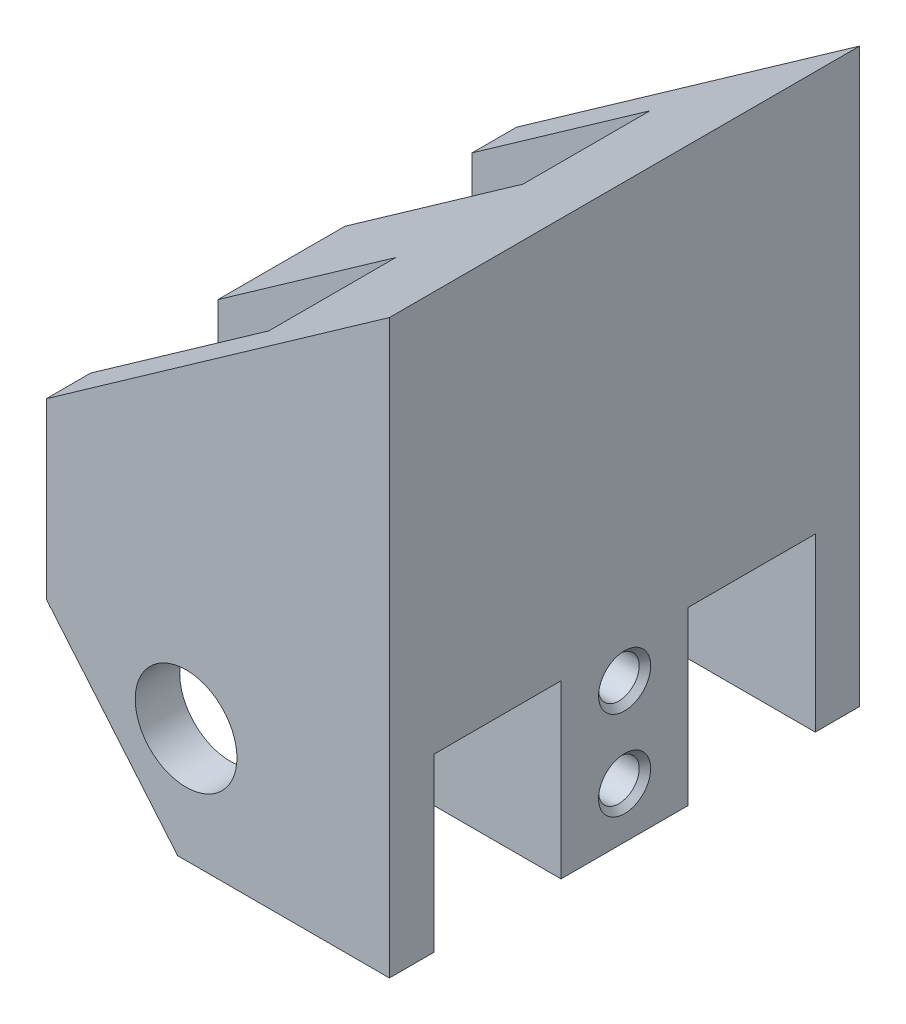
SolidWorks part; units mm, degrees
ref_plane "Front Plane" through (0, 0, 0) normal (0, 0, 1) x (1, 0, 0)
ref_plane "Top Plane" through (0, 0, 0) normal (0, 1, 0) x (1, 0, 0)
ref_plane "Right Plane" through (0, 0, 0) normal (1, 0, 0) x (0, 0, -1)
sketch "Sketch1" plane through (0, 0, 0) normal (0, 0, 1) x (1, 0, 0)
  line L0 (-7.2764, -10.5186) -> (2.2236, -16.0034)
  line L1 (2.2236, -16.0034) -> (6.2236, -16.0034)
  line L2 (-7.2764, -10.5186) -> (-7.2764, -0.5186)
  line L4 (6.2236, -16.0034) -> (6.2236, 8.9966)
  line L5 (-7.2764, -10.5186) -> (6.2236, 8.9966) construction
  line L6 (-1.4071, 3.6183) -> (6.2236, -16.0034) construction
  line L7 (-7.2764, -0.5186) -> (6.2236, 8.9966)
  point P0 (0, 0)
  dimension "D1" = 13.5
  dimension "D2" = 25
  dimension "D3" = 4
  dimension "D4" = 30
  dimension "D5" = 10
extrude "Boss-Extrude1" add sketch "Sketch1" along normal blind 18.5
sketch "Sketch2" plane through (0, 0, 0) normal (0, 0, -1) x (-1, 0, 0)
  line L0 (7.2764, -0.5186) -> (7.2764, -10.5186) construction
  line L1 (-6.2236, -16.0034) -> (-6.2236, 8.9966) construction
  line L3 (-2.2236, -16.0034) -> (-6.2236, -16.0034) construction
  circle A0 centre (1.7764, -9.0034) radius 2
  circle A1 centre (-2.2236, -5.0034) radius 1.5
  dimension "D1" = 4
  dimension "D2" = 3
  dimension "D3" = 5.5
  dimension "D4" = 4
  dimension "D5" = 7
  dimension "D6" = 11
extrude "Cut-Extrude1" cut sketch "Sketch2" against normal through all contours A0 region at (-1.7764, -9.0034, 0)
extrude "Cut-Extrude2" cut sketch "Sketch2<3>" against normal blind 11 contours A1 region at (2.2236, -5.0034, 0)
sketch "Sketch2<3>" plane through (0, 0, 0) normal (0, 0, -1) x (-1, 0, 0) same geometry as "Sketch2"
sketch "Sketch5" plane through (0, 0, 0) normal (0, 0, -1) x (-1, 0, 0)
  line L0 (-6.2236, -13.5034) -> (2.1066, -13.5034)
  line L1 (-6.2236, -16.0034) -> (-6.2236, 8.9966) construction
  line L2 (7.2764, -10.5186) -> (-2.2236, -16.0034) construction
  line L3 (2.1066, -13.5034) -> (-2.2236, -16.0034)
  line L4 (-2.2236, -16.0034) -> (-6.2236, -16.0034)
  line L5 (-6.2236, -16.0034) -> (-6.2236, -13.5034)
  dimension "D1" = 2.5
extrude "Cut-Extrude3" cut sketch "Sketch5" against normal through all
sketch "Sketch6" plane through (0, 0, 0) normal (0, 0, -1) x (-1, 0, 0)
  line L0 (2.1066, -13.5034) -> (7.2764, -7.3422)
  line L1 (7.2764, -0.5186) -> (7.2764, -10.5186) construction
  line L2 (7.2764, -7.3422) -> (7.2764, -10.5186)
  line L3 (7.2764, -10.5186) -> (2.1066, -13.5034)
  dimension "D1" = 20
extrude "Cut-Extrude4" cut sketch "Sketch6" against normal through all
sketch "Sketch7" plane through (6.2236, 0, 0) normal (1, 0, 0) x (0, 0, -1)
  line L0 (-9.25, 8.9966) -> (-9.25, -14.2492) construction
  line L1 (-18.5, 8.9966) -> (0, 8.9966) construction
  line L2 (-18.5, -13.5034) -> (0, -13.5034) construction
  line L3 (-16.75, -13.5034) -> (-11.75, -13.5034)
  line L4 (-16.75, -13.5034) -> (-16.75, -6.7534)
  line L5 (-16.75, -6.7534) -> (-11.75, -6.7534)
  line L6 (-11.75, -13.5034) -> (-11.75, -6.7534)
  line L7 (-1.75, -6.7534) -> (-6.75, -6.7534)
  line L8 (-6.75, -13.5034) -> (-6.75, -6.7534)
  line L9 (-1.75, -13.5034) -> (-6.75, -13.5034)
  line L10 (-1.75, -13.5034) -> (-1.75, -6.7534)
  line M7 (-18.5, -13.5034) -> (0, -13.5034)
  dimension "D1" = 6.75
  dimension "D2" = 5
  dimension "D3" = 2.5
extrude "Cut-Extrude5" cut sketch "Sketch7" against normal through all contours L6 L5 L4 M7 | L10 L7 L8 M7 region at (6.2236, -10.1284, 14.25) region at (6.2236, -10.1284, 4.25)
hole_wizard "M2x0.4 Tapped Hole1" positions "Sketch9" profile "Sketch10" tap size "M2x0.4" standard "ANSI Metric"
sketch "Sketch9" plane through (6.2236, 0, 0) normal (1, 0, 0) x (0, 0, -1)
  line L0 (-11.75, -13.5034) -> (-6.75, -13.5034) construction
  line L1 (-11.75, -13.5034) -> (-11.75, -6.7534) construction
  point P0 (-9.25, -8.0034)
  point P2 (-9.25, -11.5034)
  dimension "D1" = 2
  dimension "D2" = 3.5
  dimension "D3" = 2.5
  dimension "D4" = 2.5
cosmetic thread "Hole Thread1" parameters "D1"=6.07, "D2"=2
cosmetic thread "Hole Thread2" parameters "D1"=6.07, "D2"=2
sketch "Sketch10" plane through (6.2236, -8.0034, 9.25) normal (0, 1, 0) x (0, 0, -1)
  line L0 (0, 0) -> (0, 5.4807)
  line L1 (0, 5.4807) -> (0.8, 5)
  line L2 (0.8, 5) -> (0.8, 0.225)
  line L3 (0.8, 0.225) -> (1.025, 0)
  line L5 (1.025, 0) -> (0, 0)
  line L6 (-0.8, 0.225) -> (-1.025, 0) construction
  line L10 (0, 5.4807) -> (-0.8, 5) construction
  line L11 (0, -6.35) -> (0, 107.95) construction
  dimension "Tap Drill Dia." = 1.6
  dimension "Tap Drill Depth" = 5
  dimension "Near C'Sink Dia." = 2.05
  dimension "Near C'Sink Angle" = 90
  dimension "Drill Angle" = 118
sketch "Sketch11" plane through (0, -6.7534, 0) normal (0, -1, 0) x (1, 0, 0)
  line L0 (-7.2764, 16.75) -> (6.2236, 16.75) construction
  line L1 (-0.2764, 16.75) -> (-7.2764, 16.75)
  line L2 (-0.2764, 16.75) -> (-0.2764, 11.75)
  line L3 (-0.2764, 11.75) -> (-7.2764, 11.75)
  line L4 (-7.2764, 16.75) -> (-7.2764, 11.75)
  line L5 (-7.2764, 6.75) -> (6.2236, 6.75) construction
  line L6 (-7.2764, 1.75) -> (6.2236, 1.75) construction
  line L7 (-7.2764, 1.75) -> (-0.2764, 1.75)
  line L8 (-7.2764, 1.75) -> (-7.2764, 6.75)
  line L9 (-7.2764, 6.75) -> (-0.2764, 6.75)
  line L10 (-0.2764, 1.75) -> (-0.2764, 6.75)
  line L11 (-2.1066, 1.75) -> (6.2236, 1.75) construction
  line L12 (-7.2764, 1.75) -> (-7.2764, 6.75) construction
  point P15 (-7.2764, 6.75)
  point P19 (0, 0)
  point P20 (0, 0)
  point P21 (0, 0)
  dimension "D1" = 7
  dimension "D2" = 7
  dimension "D3" = 5
extrude "Cut-Extrude6" cut sketch "Sketch11" against normal through all
